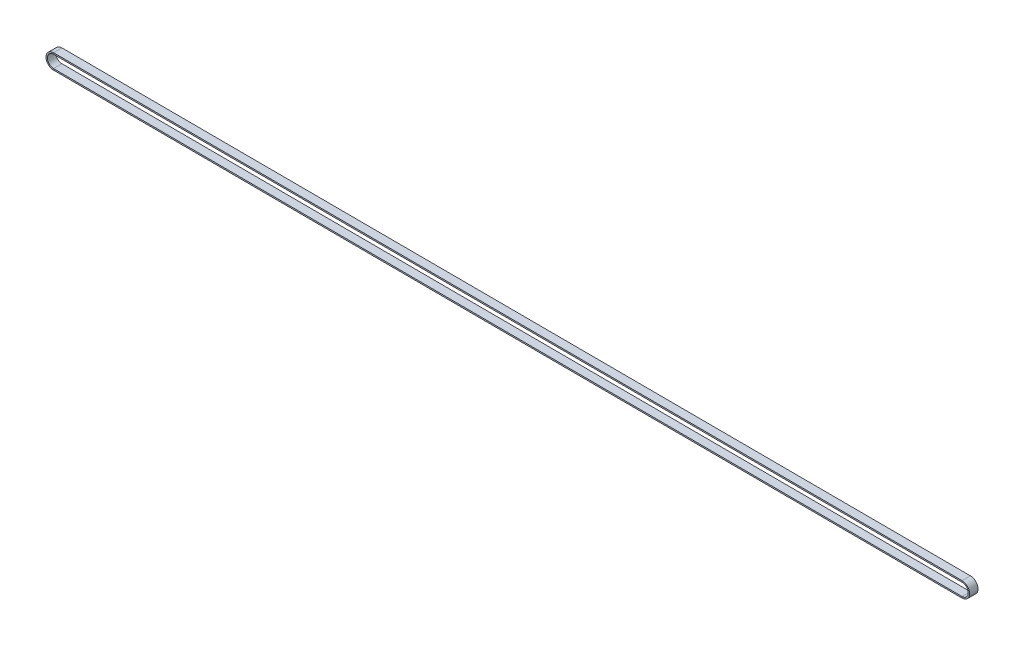
SolidWorks part; units mm, degrees
ref_plane "Front Plane" through (0, 0, 0) normal (0, 0, 1) x (1, 0, 0)
ref_plane "Top Plane" through (0, 0, 0) normal (0, 1, 0) x (1, 0, 0)
ref_plane "Right Plane" through (0, 0, 0) normal (1, 0, 0) x (0, 0, -1)
sketch "Sketch2" plane through (0, 0, 0) normal (0, 0, 1) x (1, 0, 0)
  line L0 (0, 0) -> (1, 0) construction
  line L1 (0, 0) -> (0, 1) construction
  line L2 (-6.4316, 34.2653) -> (-982.7572, 37.4611)
  line L3 (-982.704, 53.7405) -> (-6.3783, 50.5447)
  arc A0 (-6.3783, 50.5447) -> (-6.4316, 34.2653) centre (-6.4049, 42.405) cw
  arc A1 (-982.7572, 37.4611) -> (-982.704, 53.7405) centre (-982.7306, 45.6008) cw
ref_plane "Plane1" through (-6.3783, 50.5447, 0) normal (1, -0.0033, 0) x (0, 0, -1)
sketch "Sketch3" plane through (-6.3783, 50.5447, 0) normal (1, -0.0033, 0) x (0, 0, -1)
  line L1 (0, -1.5) -> (9, -1.5)
  line L2 (0, -1.5) -> (0, 0)
  line L3 (0, 0) -> (9, 0)
  line L4 (9, -1.5) -> (9, 0)
  dimension "D1" = 1.5
  dimension "D2" = 9
sweep "Sweep1" add profiles "Sketch3" path "Sketch2"
